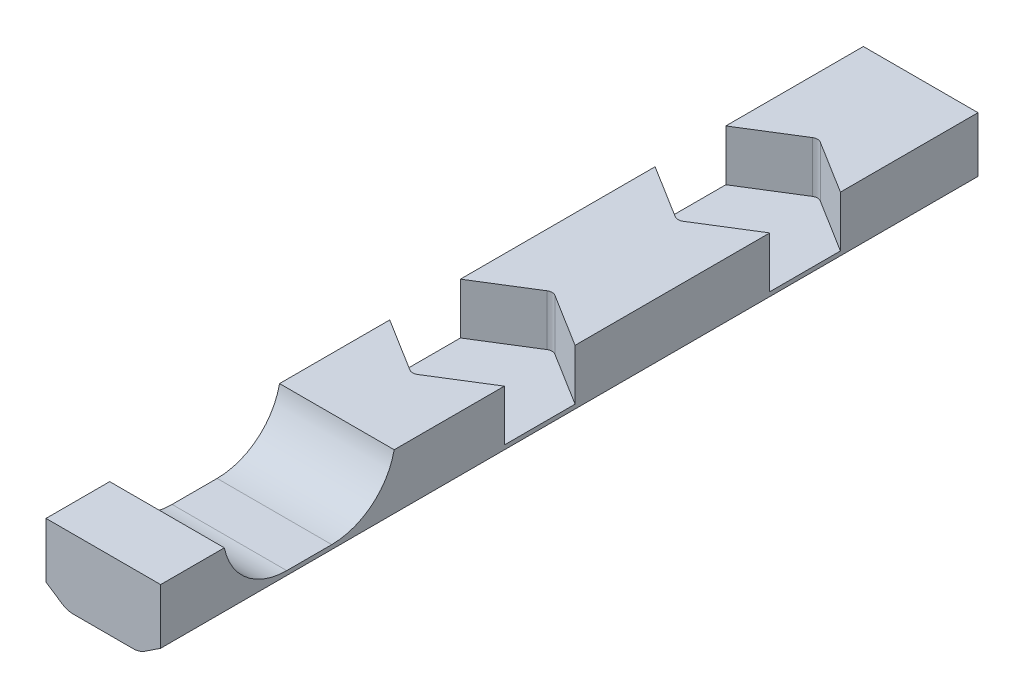
SolidWorks part; units mm, degrees
ref_plane "Front Plane" through (0, 0, 0) normal (0, 0, 1) x (1, 0, 0)
ref_plane "Top Plane" through (0, 0, 0) normal (0, 1, 0) x (1, 0, 0)
ref_plane "Right Plane" through (0, 0, 0) normal (1, 0, 0) x (0, 0, -1)
sketch "Sketch1" plane through (0, 0, 0) normal (0, 0, 1) x (1, 0, 0)
  line L0 (0, 0) -> (3.4, 0)
  line L1 (3.4, 0) -> (4.4, 0.6633)
  line L2 (4.4, 0.6633) -> (4.4, 3.2633)
  line L3 (4.4, 3.2633) -> (-1, 3.2633)
  line L4 (-1, 3.2633) -> (-1, 0.6633)
  line L5 (-1, 0.6633) -> (0, 0)
  dimension "D1" = 5.4
  dimension "D2" = 3.4
  dimension "D3" = 1.2
  dimension "D4" = 2.6
  dimension "D5" = 2.6
  dimension "D6" = 1.2
extrude "Boss-Extrude1" add sketch "Sketch1" along normal blind 38.5
fillet "Fillet3" radius 1 1 edges at (3.4, 0, 19.25)
fillet "Fillet4" radius 1 1 edges at (0, 0, 19.25)
sketch "Sketch2" plane through (0, 3.2633, 0) normal (0, 1, 0) x (1, 0, 0)
  line L0 (4.4, -9.81) -> (4.4, -6.48)
  line L1 (4.4, -38.5) -> (4.4, 0) construction
  line L2 (4.4, -6.48) -> (1.7, -4.8)
  line L3 (1.7, -4.8) -> (-1, -6.48)
  line L4 (-1, -38.5) -> (-1, 0) construction
  line L5 (-1, -6.48) -> (-1, -9.81)
  line L6 (-1, -9.81) -> (1.7, -11.49)
  line L7 (1.7, -11.49) -> (4.4, -9.81)
  line L8 (4.4, 0) -> (-1, 0) construction
  dimension "D1" = 3.18
  dimension "D2" = 3.18
  dimension "D3" = 3.18
  dimension "D4" = 3.18
  dimension "D5" = 3.33
  dimension "D6" = 5.4
  dimension "D7" = 3.33
  dimension "D8" = 4.8
extrude "Cut-Extrude1" cut sketch "Sketch2" against normal blind 2.4
pattern_linear "LPattern1" count 2 spacing 12.5 along (0, 0, 1) of "Cut-Extrude1"
sketch "Sketch3" plane through (0, 3.2633, 0) normal (0, 1, 0) x (1, 0, 0)
  line L0 (-1, -38.5) -> (-1, -22.31) construction
  line L1 (-1, -35.5) -> (4.4, -35.5)
  line L2 (-1, -35.5) -> (-1, -27.5)
  line L3 (-1, -27.5) -> (4.4, -27.5)
  line L4 (4.4, -35.5) -> (4.4, -27.5)
  line L5 (4.4, -38.5) -> (4.4, -22.31) construction
  line L6 (4.4, -38.5) -> (-1, -38.5) construction
  dimension "D1" = 3
  dimension "D2" = 8
extrude "Cut-Extrude2" cut sketch "Sketch3" against normal blind 2.4
fillet "Fillet5" radius 3 2 edges at (1.7, 0.8633, 27.5) (1.7, 0.8633, 35.5)
fillet "Fillet6" radius 0.35 4 edges at (1.7, 2.0633, 17.3) (1.7, 2.0633, 23.99) (1.7, 2.0633, 4.8) (1.7, 2.0633, 11.49)
